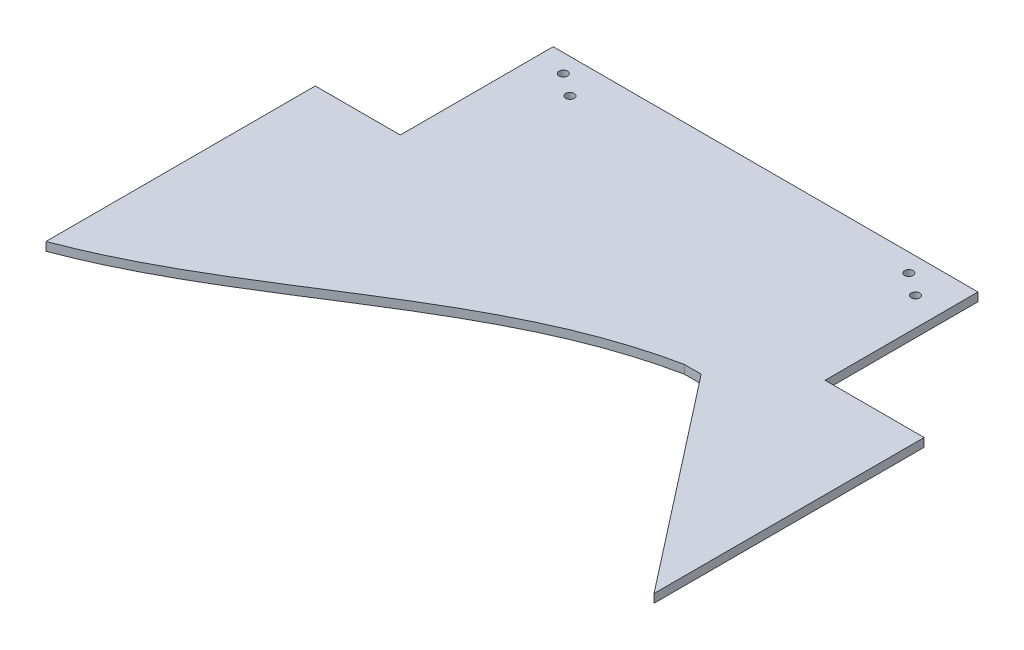
SolidWorks part; units mm, degrees
ref_plane "Front Plane" through (0, 0, 0) normal (0, 0, 1) x (1, 0, 0)
ref_plane "Top Plane" through (0, 0, 0) normal (0, 1, 0) x (1, 0, 0)
ref_plane "Right Plane" through (0, 0, 0) normal (1, 0, 0) x (0, 0, -1)
sketch "Sketch1" plane through (0, 0, 0) normal (0, 1, 0) x (1, 0, 0)
  line L0 (-75, -37) -> (-75, -97)
  line L1 (-75, -37) -> (75, -37)
  line L2 (-75, -37) -> (-75, 37)
  line L3 (-75, 37) -> (75, 37)
  line L4 (75, -37) -> (75, 37)
  line L5 (-75, -37) -> (75, 37) construction
  line L6 (-75, 37) -> (75, -37) construction
  line L7 (-105, -112.092) -> (-105, -97)
  line L8 (110, -112.3923) -> (51.2597, -37)
  line L9 (80.6299, -74.6961) -> (87.2068, -112.3923)
  line L10 (87.2068, -112.3923) -> (110, -112.3923)
  line L11 (-75, -17) -> (-105, -17)
  line L12 (-75, -17) -> (-75, -97)
  line L13 (-75, -97) -> (-105, -97)
  line L14 (-105, -17) -> (-105, -97)
  line L15 (75, -17) -> (110, -17)
  line L18 (110, -17) -> (110, -112.3923)
  circle A0 centre (40, -64.1393) radius 25 construction
  circle A1 centre (-65, 30.5733) radius 1.5
  circle A2 centre (-57, 24.9128) radius 1.5
  circle A3 centre (57, 30.5733) radius 1.5
  circle A4 centre (65, 24.9128) radius 1.5
  spline S0 degree 3 poles (45.2815, -37) (-12.2847, -48.6892) (-51.8248, -92.3041) (-105, -112.092) knots 0 0 0 0 1 1 1 1
  point P0 (0, 0)
  point P27 (0, 0)
  point P28 (0, 0)
  dimension "D8" = 50
  dimension "D7" = 3
  dimension "D10" = 3
  dimension "D11" = 3
  dimension "D12" = 3
  dimension "D1" = 150
  dimension "D2" = 74
  dimension "D3" = 35
  dimension "D4" = 60
  dimension "D5" = 80
  dimension "D6" = 30
  dimension "D9" = 35
  dimension "D13" = 10
  dimension "D14" = 8
  dimension "D15" = 10
  dimension "D16" = 8
extrude "Boss-Extrude1" add sketch "Sketch1" along normal blind 3 contours L0 L1 | L1 L4 L3 L2 | L1 | L12 L11 L14 L13 region at (-43.1942, 0, 60.2298) region at (0, 0, 0.0708) region at (90.9195, 0, 53.6925)
sketch "Sketch2" plane through (0, 3, 0) normal (0, 1, 0) x (1, 0, 0)
  line L0 (75, -17) -> (75, 37) construction
  circle A0 centre (40, -67.3967) radius 25 construction
  dimension "D1" = 50
  dimension "D2" = 35
